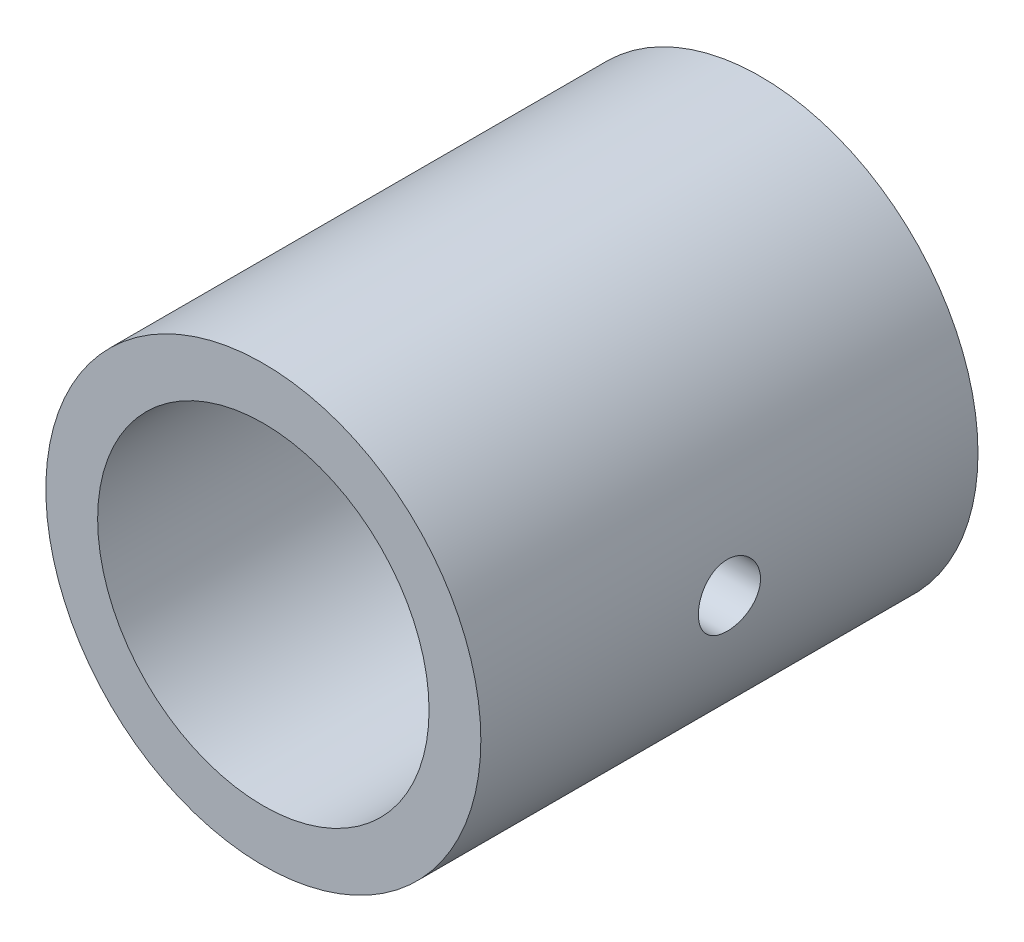
SolidWorks part; units mm, degrees
ref_plane "Front Plane" through (0, 0, 0) normal (0, 0, 1) x (1, 0, 0)
ref_plane "Top Plane" through (0, 0, 0) normal (0, 1, 0) x (1, 0, 0)
ref_plane "Right Plane" through (0, 0, 0) normal (1, 0, 0) x (0, 0, -1)
sketch "Sketch1" plane through (0, 0, 0) normal (0, 0, 1) x (1, 0, 0)
  circle A0 centre (0, 0) radius 5.25
  dimension "D1" = 10.5
extrude "Boss-Extrude1" add sketch "Sketch1" along normal blind 12
sketch "Sketch2" plane through (0, 0, 12) normal (0, 0, 1) x (1, 0, 0)
  circle A0 centre (0, 0) radius 4
  dimension "D1" = 8
extrude "Cut-Extrude1" cut sketch "Sketch2" against normal blind 15
sketch "Sketch3" plane through (0, 0, 0) normal (1, 0, 0) x (0, 0, -1)
  line L0 (-12, 0) -> (0, 0) construction
  line L1 (-12, 5.25) -> (-12, -5.25) construction
  line L2 (0, -5.25) -> (0, 5.25) construction
  circle A0 centre (-6, 0) radius 0.75
  point P8 (-6, 0)
  dimension "D1" = 1.5
extrude "Cut-Extrude2" cut sketch "Sketch3" against normal through all both and the other way through all
